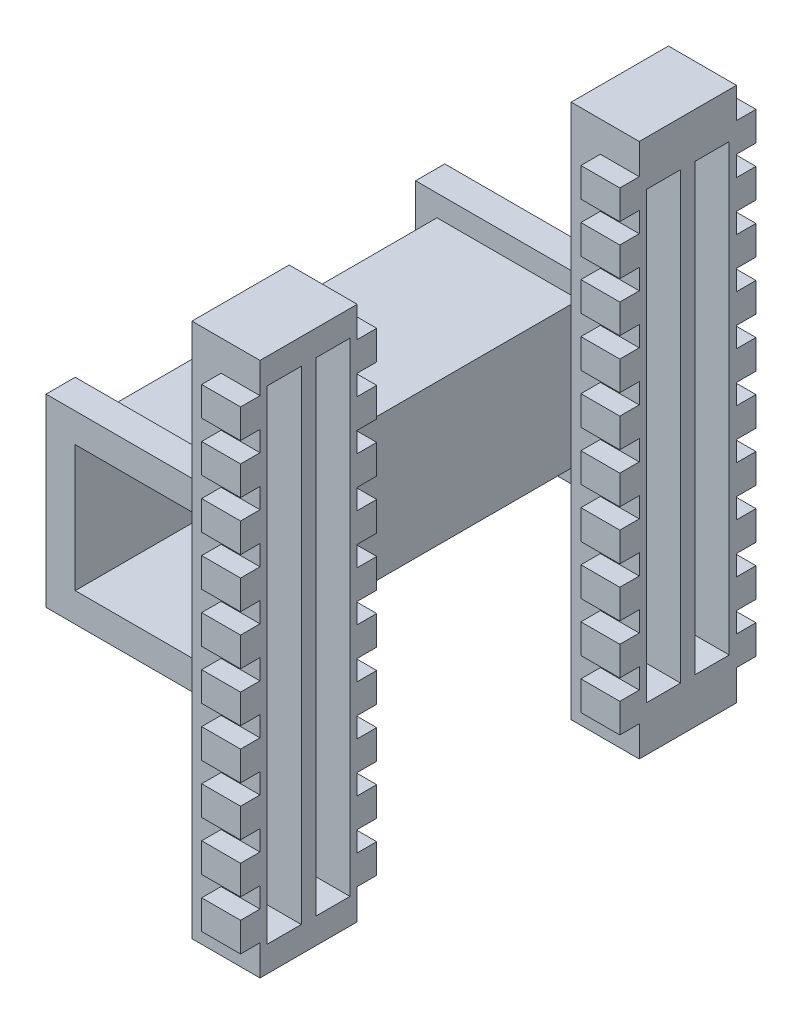
SolidWorks part; units mm, degrees
ref_plane "前视基准面" through (0, 0, 0) normal (0, 0, 1) x (1, 0, 0)
ref_plane "上视基准面" through (0, 0, 0) normal (0, 1, 0) x (1, 0, 0)
ref_plane "右视基准面" through (0, 0, 0) normal (1, 0, 0) x (0, 0, -1)
sketch "草图1" plane through (0, 0, 0) normal (0, 0, 1) x (1, 0, 0)
  line L0 (0.8, 0.8) -> (13.8, 0.8)
  line L5 (0, 0) -> (14.6, 0)
  line L6 (0, 0) -> (0, 14.6)
  line L7 (0, 14.6) -> (14.6, 14.6)
  line L9 (13.8, 0.8) -> (13.8, 13.8)
  line L10 (0.8, 13.8) -> (13.8, 13.8)
  line L11 (0.8, 0.8) -> (0.8, 13.8)
  line L13 (16.8, 14.6) -> (16.8, 0)
  line L15 (16.8, 7.3) -> (16.8, 34.8)
  line L16 (16.8, 7.3) -> (16.8, -20.2)
  line L17 (16.8, 34.8) -> (23.8, 34.8)
  line L18 (23.8, 34.8) -> (23.8, -20.2)
  line L19 (23.8, -20.2) -> (16.8, -20.2)
  line L23 (14.6, 14.6) -> (14.6, 0)
  line L24 (16.8, 0) -> (16.8, 14.6)
  line L28 (14.6, -2.2) -> (-2.2, -2.2)
  line L29 (-2.2, -2.2) -> (-2.2, 16.8)
  line L30 (-2.2, 16.8) -> (16.8, 16.8)
  line L31 (16.8, 16.8) -> (16.8, -2.2)
  line L32 (16.8, -2.2) -> (14.6, -2.2)
  line L34 (14.6, 0) -> (14.6, 14.6) construction
  point P14 (0, 0)
  dimension "D1" = 0.8
extrude "凸台-拉伸4" add sketch "草图1" along normal mid plane 41 contours L7 L23 L5 L6 | L10 L9 L0 L11
extrude "凸台-拉伸8" add sketch "草图1<12>" along normal mid plane 41 contours L32 L16 L13 L15 L30 L29 L28 L7 L23 L5 L6 region at (16.5313, 10.95, 0)
sketch "草图1<12>" plane through (0, 0, 0) normal (0, 0, 1) x (1, 0, 0) same geometry as "草图1"
extrude "切除-拉伸3" cut sketch "草图1<13>" against normal mid plane 35 contours L32 L28 L29 L30 L31 | L5 L23 L7 L6
sketch "草图1<13>" plane through (0, 0, 0) normal (0, 0, 1) x (1, 0, 0) same geometry as "草图1"
extrude "凸台-拉伸9" add sketch "草图1<14>" along normal mid plane 53 contours L19 L18 L17 L15 L13 L16 region at (20.3, 7.3, 0)
sketch "草图1<14>" plane through (0, 0, 0) normal (0, 0, 1) x (1, 0, 0) same geometry as "草图1"
extrude "切除-拉伸4" cut sketch "草图1<15>" against normal mid plane 25 contours L18 L19 L16 L15 L17
sketch "草图1<15>" plane through (0, 0, 0) normal (0, 0, 1) x (1, 0, 0) same geometry as "草图1"
sketch "草图6" plane through (0, 0, -26.5) normal (0, 0, -1) x (-1, 0, 0)
  line L3 (-23.8, 31.66) -> (-19.8, 31.66)
  line L5 (-23.8, 31.66) -> (-23.8, 28.66)
  line L7 (-23.8, 28.66) -> (-19.8, 28.66)
  line L8 (-23.8, -20.2) -> (-16.8, -20.2)
  line L9 (-19.8, 31.66) -> (-19.8, 28.66)
  line L10 (-16.8, -20.2) -> (-16.8, 34.8)
  line L11 (-23.8, 31.66) -> (-19.8, 28.66) construction
  line L12 (-16.8, 34.8) -> (-23.8, 34.8)
  line L13 (-23.8, 28.66) -> (-19.8, 31.66) construction
  line L14 (-23.8, 34.8) -> (-23.8, -20.2)
  line L15 (-23.8, 26.58) -> (-19.8, 26.58)
  line L16 (-23.8, -20.2) -> (-16.8, -20.2)
  line L17 (-23.8, 26.58) -> (-23.8, 23.58)
  line L18 (-16.8, -20.2) -> (-16.8, 34.8)
  line L19 (-23.8, 23.58) -> (-19.8, 23.58)
  line L20 (-16.8, 34.8) -> (-23.8, 34.8)
  line L21 (-19.8, 26.58) -> (-19.8, 23.58)
  line L22 (-23.8, 26.58) -> (-19.8, 23.58) construction
  line L23 (-23.8, 23.58) -> (-19.8, 26.58) construction
  line L24 (-23.8, 21.5) -> (-19.8, 21.5)
  line L25 (-23.8, 21.5) -> (-23.8, 18.5)
  line L26 (-23.8, 18.5) -> (-19.8, 18.5)
  line L27 (-19.8, 21.5) -> (-19.8, 18.5)
  line L28 (-23.8, 21.5) -> (-19.8, 18.5) construction
  line L29 (-23.8, 18.5) -> (-19.8, 21.5) construction
  line L30 (-23.8, 16.42) -> (-19.8, 16.42)
  line L31 (-23.8, 16.42) -> (-23.8, 13.42)
  line L32 (-23.8, 13.42) -> (-19.8, 13.42)
  line L33 (-19.8, 16.42) -> (-19.8, 13.42)
  line L34 (-23.8, 16.42) -> (-19.8, 13.42) construction
  line L35 (-23.8, 13.42) -> (-19.8, 16.42) construction
  line L36 (-23.8, 11.34) -> (-19.8, 11.34)
  line L37 (-23.8, 11.34) -> (-23.8, 8.34)
  line L38 (-23.8, 8.34) -> (-19.8, 8.34)
  line L39 (-19.8, 11.34) -> (-19.8, 8.34)
  line L40 (-23.8, 11.34) -> (-19.8, 8.34) construction
  line L41 (-23.8, 8.34) -> (-19.8, 11.34) construction
  line L42 (-23.8, 6.26) -> (-19.8, 6.26)
  line L43 (-23.8, 6.26) -> (-23.8, 3.26)
  line L44 (-23.8, 3.26) -> (-19.8, 3.26)
  line L45 (-19.8, 6.26) -> (-19.8, 3.26)
  line L46 (-23.8, 6.26) -> (-19.8, 3.26) construction
  line L47 (-23.8, 3.26) -> (-19.8, 6.26) construction
  line L48 (-23.8, 1.1866) -> (-19.8, 1.1866)
  line L49 (-23.8, 1.1866) -> (-23.8, -1.8266)
  line L50 (-23.8, -1.8266) -> (-19.8, -1.8266)
  line L51 (-19.8, 1.1866) -> (-19.8, -1.8266)
  line L52 (-23.8, 1.1866) -> (-19.8, -1.8266) construction
  line L53 (-23.8, -1.8266) -> (-19.8, 1.1866) construction
  line L54 (-23.8, -3.9) -> (-19.8, -3.9)
  line L55 (-23.8, -3.9) -> (-23.8, -6.9)
  line L56 (-23.8, -6.9) -> (-19.8, -6.9)
  line L57 (-19.8, -3.9) -> (-19.8, -6.9)
  line L58 (-23.8, -3.9) -> (-19.8, -6.9) construction
  line L59 (-23.8, -6.9) -> (-19.8, -3.9) construction
  line L60 (-23.8, -8.98) -> (-19.8, -8.98)
  line L61 (-23.8, -8.98) -> (-23.8, -11.98)
  line L62 (-23.8, -11.98) -> (-19.8, -11.98)
  line L63 (-19.8, -8.98) -> (-19.8, -11.98)
  line L64 (-23.8, -8.98) -> (-19.8, -11.98) construction
  line L65 (-23.8, -11.98) -> (-19.8, -8.98) construction
  line L66 (-23.8, -14.06) -> (-19.8, -14.06)
  line L67 (-23.8, -14.06) -> (-23.8, -17.06)
  line L68 (-23.8, -17.06) -> (-19.8, -17.06)
  line L69 (-19.8, -14.06) -> (-19.8, -17.06)
  line L70 (-23.8, -14.06) -> (-19.8, -17.06) construction
  line L71 (-23.8, -17.06) -> (-19.8, -14.06) construction
  line L72 (-23.8, 34.8) -> (-23.8, -20.2)
  point P0 (-21.8, 30.16)
  point P27 (-21.8, 25.08)
  point P32 (-21.8, 20)
  point P37 (-21.8, 14.92)
  point P42 (-21.8, 9.84)
  point P47 (-21.8, 4.76)
  point P52 (-21.8, -0.32)
  point P57 (-21.8, -5.4)
  point P62 (-21.8, -10.48)
  point P67 (-21.8, -15.56)
  line M14 (-23.8, -20.2) -> (-16.8, -20.2)
  line M15 (-16.8, -20.2) -> (-16.8, 34.8)
  line M16 (-16.8, 34.8) -> (-23.8, 34.8)
  line M17 (-23.8, 34.8) -> (-23.8, -20.2)
  dimension "D1" = 0
extrude "切除-拉伸5" cut sketch "草图6" against normal blind 2 contours L66 L69 L68 L3 L9 L7 L15 L21 L19 L24 L27 L26 L30 L33 L32 L36 L39 L38 L42 L45 L44 L48 L51 L50 L54 L57 L56 L60 L63 L62 M17 M14 M15 M16 region at (19.6203, 7.3015, -26.5)
sketch "草图7" plane through (0, 0, -12.5) normal (0, 0, 1) x (1, 0, 0)
  line L0 (19.8, -17.06) -> (19.8, -14.06) construction
  line L1 (19.8, -14.06) -> (23.8, -14.06) construction
  line L2 (23.8, -14.06) -> (23.8, -17.06) construction
  line L3 (23.8, -17.06) -> (19.8, -17.06) construction
  line L4 (23.8, 34.8) -> (16.8, 34.8)
  line L5 (16.8, 34.8) -> (16.8, -20.2)
  line L6 (16.8, -20.2) -> (23.8, -20.2)
  line L7 (23.8, -20.2) -> (23.8, 34.8)
  line L8 (23.8, 34.8) -> (16.8, 34.8)
  line L9 (16.8, 34.8) -> (16.8, -20.2)
  line L10 (16.8, -20.2) -> (23.8, -20.2)
  line L11 (23.8, -20.2) -> (23.8, 34.8)
  line L12 (23.8, -11.98) -> (19.8, -11.98) construction
  line L13 (19.8, -11.98) -> (19.8, -8.98) construction
  line L14 (19.8, -8.98) -> (23.8, -8.98) construction
  line L15 (23.8, -8.98) -> (23.8, -11.98) construction
  line L16 (23.8, -6.9) -> (19.8, -6.9) construction
  line L17 (19.8, -6.9) -> (19.8, -3.9) construction
  line L18 (19.8, -3.9) -> (23.8, -3.9) construction
  line L19 (23.8, -3.9) -> (23.8, -6.9) construction
  line L20 (23.8, -1.8266) -> (19.8, -1.8266) construction
  line L21 (19.8, -1.8266) -> (19.8, 1.1866) construction
  line L22 (19.8, 1.1866) -> (23.8, 1.1866) construction
  line L23 (23.8, 1.1866) -> (23.8, -1.8266) construction
  line L24 (23.8, 3.26) -> (19.8, 3.26) construction
  line L25 (19.8, 3.26) -> (19.8, 6.26) construction
  line L26 (19.8, 6.26) -> (23.8, 6.26) construction
  line L27 (23.8, 6.26) -> (23.8, 3.26) construction
  line L28 (23.8, 8.34) -> (19.8, 8.34) construction
  line L29 (19.8, 8.34) -> (19.8, 11.34) construction
  line L30 (19.8, 11.34) -> (23.8, 11.34) construction
  line L31 (23.8, 11.34) -> (23.8, 8.34) construction
  line L32 (23.8, 13.42) -> (19.8, 13.42) construction
  line L33 (19.8, 13.42) -> (19.8, 16.42) construction
  line L34 (19.8, 16.42) -> (23.8, 16.42) construction
  line L35 (23.8, 16.42) -> (23.8, 13.42) construction
  line L36 (23.8, 18.5) -> (19.8, 18.5) construction
  line L37 (19.8, 18.5) -> (19.8, 21.5) construction
  line L38 (19.8, 21.5) -> (23.8, 21.5) construction
  line L39 (23.8, 21.5) -> (23.8, 18.5) construction
  line L40 (23.8, 23.58) -> (19.8, 23.58) construction
  line L41 (19.8, 23.58) -> (19.8, 26.58) construction
  line L42 (19.8, 26.58) -> (23.8, 26.58) construction
  line L43 (23.8, 26.58) -> (23.8, 23.58) construction
  line L44 (23.8, 28.66) -> (19.8, 28.66) construction
  line L45 (19.8, 28.66) -> (19.8, 31.66) construction
  line L46 (19.8, 31.66) -> (23.8, 31.66) construction
  line L47 (23.8, 31.66) -> (23.8, 28.66) construction
  line L48 (19.8, -17.06) -> (19.8, -14.06)
  line L49 (19.8, -14.06) -> (23.8, -14.06)
  line L50 (23.8, -14.06) -> (23.8, -17.06)
  line L51 (23.8, -17.06) -> (19.8, -17.06)
  line L52 (23.8, -11.98) -> (19.8, -11.98)
  line L53 (19.8, -11.98) -> (19.8, -8.98)
  line L54 (19.8, -8.98) -> (23.8, -8.98)
  line L55 (23.8, -8.98) -> (23.8, -11.98)
  line L56 (23.8, -6.9) -> (19.8, -6.9)
  line L57 (19.8, -6.9) -> (19.8, -3.9)
  line L58 (19.8, -3.9) -> (23.8, -3.9)
  line L59 (23.8, -3.9) -> (23.8, -6.9)
  line L60 (23.8, -1.8266) -> (19.8, -1.8266)
  line L61 (19.8, -1.8266) -> (19.8, 1.1866)
  line L62 (19.8, 1.1866) -> (23.8, 1.1866)
  line L63 (23.8, 1.1866) -> (23.8, -1.8266)
  line L64 (23.8, 3.26) -> (19.8, 3.26)
  line L65 (19.8, 3.26) -> (19.8, 6.26)
  line L66 (19.8, 6.26) -> (23.8, 6.26)
  line L67 (23.8, 6.26) -> (23.8, 3.26)
  line L68 (23.8, 8.34) -> (19.8, 8.34)
  line L69 (19.8, 8.34) -> (19.8, 11.34)
  line L70 (19.8, 11.34) -> (23.8, 11.34)
  line L71 (23.8, 11.34) -> (23.8, 8.34)
  line L72 (23.8, 13.42) -> (19.8, 13.42)
  line L73 (19.8, 13.42) -> (19.8, 16.42)
  line L74 (19.8, 16.42) -> (23.8, 16.42)
  line L75 (23.8, 16.42) -> (23.8, 13.42)
  line L76 (23.8, 18.5) -> (19.8, 18.5)
  line L77 (19.8, 18.5) -> (19.8, 21.5)
  line L78 (19.8, 21.5) -> (23.8, 21.5)
  line L79 (23.8, 21.5) -> (23.8, 18.5)
  line L80 (23.8, 23.58) -> (19.8, 23.58)
  line L81 (19.8, 23.58) -> (19.8, 26.58)
  line L82 (19.8, 26.58) -> (23.8, 26.58)
  line L83 (23.8, 26.58) -> (23.8, 23.58)
  line L84 (23.8, 28.66) -> (19.8, 28.66)
  line L85 (19.8, 28.66) -> (19.8, 31.66)
  line L86 (19.8, 31.66) -> (23.8, 31.66)
  line L87 (23.8, 31.66) -> (23.8, 28.66)
  line M5 (23.8, 34.8) -> (16.8, 34.8)
  line M6 (16.8, 34.8) -> (16.8, -20.2)
  line M7 (16.8, -20.2) -> (23.8, -20.2)
  line M8 (23.8, -20.2) -> (23.8, 34.8)
  dimension "D1" = 0
extrude "切除-拉伸6" cut sketch "草图7" against normal blind 2 contours L85 L86 L11 L51 L48 L49 L52 L53 L54 L56 L57 L58 L60 L61 L62 L64 L65 L66 L68 L69 L70 L72 L73 L74 L76 L77 L78 L80 L81 L82 L84 M5 M6 M7 M8 region at (19.6203, 7.3015, -12.5)
sketch "草图8" plane through (0, 0, 12.5) normal (0, 0, -1) x (-1, 0, 0)
  line L0 (-23.8, 13.42) -> (-19.8, 13.42) construction
  line L1 (-19.8, 13.42) -> (-19.8, 16.42) construction
  line L2 (-19.8, 16.42) -> (-23.8, 16.42) construction
  line L3 (-23.8, 16.42) -> (-23.8, 13.42) construction
  line L4 (-16.8, 34.8) -> (-23.8, 34.8)
  line L5 (-23.8, 34.8) -> (-23.8, -20.2)
  line L6 (-23.8, -20.2) -> (-16.8, -20.2)
  line L7 (-16.8, -20.2) -> (-16.8, 34.8)
  line L8 (-16.8, 34.8) -> (-23.8, 34.8)
  line L9 (-23.8, 34.8) -> (-23.8, -20.2)
  line L10 (-23.8, -20.2) -> (-16.8, -20.2)
  line L11 (-16.8, -20.2) -> (-16.8, 34.8)
  line L12 (-23.8, 18.5) -> (-19.8, 18.5) construction
  line L13 (-19.8, 18.5) -> (-19.8, 21.5) construction
  line L14 (-19.8, 21.5) -> (-23.8, 21.5) construction
  line L15 (-23.8, 21.5) -> (-23.8, 18.5) construction
  line L16 (-23.8, 23.58) -> (-19.8, 23.58) construction
  line L17 (-19.8, 23.58) -> (-19.8, 26.58) construction
  line L18 (-19.8, 26.58) -> (-23.8, 26.58) construction
  line L19 (-23.8, 26.58) -> (-23.8, 23.58) construction
  line L20 (-23.8, 28.66) -> (-19.8, 28.66) construction
  line L21 (-19.8, 28.66) -> (-19.8, 31.66) construction
  line L22 (-19.8, 31.66) -> (-23.8, 31.66) construction
  line L23 (-23.8, 31.66) -> (-23.8, 28.66) construction
  line L24 (-23.8, 8.34) -> (-19.8, 8.34) construction
  line L25 (-19.8, 8.34) -> (-19.8, 11.34) construction
  line L26 (-19.8, 11.34) -> (-23.8, 11.34) construction
  line L27 (-23.8, 11.34) -> (-23.8, 8.34) construction
  line L28 (-23.8, 3.26) -> (-19.8, 3.26) construction
  line L29 (-19.8, 3.26) -> (-19.8, 6.26) construction
  line L30 (-19.8, 6.26) -> (-23.8, 6.26) construction
  line L31 (-23.8, 6.26) -> (-23.8, 3.26) construction
  line L32 (-23.8, -1.8266) -> (-19.8, -1.8266) construction
  line L33 (-19.8, -1.8266) -> (-19.8, 1.1866) construction
  line L34 (-19.8, 1.1866) -> (-23.8, 1.1866) construction
  line L35 (-23.8, 1.1866) -> (-23.8, -1.8266) construction
  line L36 (-23.8, -6.9) -> (-19.8, -6.9) construction
  line L37 (-19.8, -6.9) -> (-19.8, -3.9) construction
  line L38 (-19.8, -3.9) -> (-23.8, -3.9) construction
  line L39 (-23.8, -3.9) -> (-23.8, -6.9) construction
  line L40 (-23.8, -11.98) -> (-19.8, -11.98) construction
  line L41 (-19.8, -11.98) -> (-19.8, -8.98) construction
  line L42 (-19.8, -8.98) -> (-23.8, -8.98) construction
  line L43 (-23.8, -8.98) -> (-23.8, -11.98) construction
  line L44 (-19.8, -17.06) -> (-19.8, -14.06) construction
  line L45 (-19.8, -14.06) -> (-23.8, -14.06) construction
  line L46 (-23.8, -14.06) -> (-23.8, -17.06) construction
  line L47 (-23.8, -17.06) -> (-19.8, -17.06) construction
  line L48 (-23.8, 13.42) -> (-19.8, 13.42)
  line L49 (-19.8, 13.42) -> (-19.8, 16.42)
  line L50 (-19.8, 16.42) -> (-23.8, 16.42)
  line L51 (-23.8, 16.42) -> (-23.8, 13.42)
  line L52 (-23.8, 18.5) -> (-19.8, 18.5)
  line L53 (-19.8, 18.5) -> (-19.8, 21.5)
  line L54 (-19.8, 21.5) -> (-23.8, 21.5)
  line L55 (-23.8, 21.5) -> (-23.8, 18.5)
  line L56 (-23.8, 23.58) -> (-19.8, 23.58)
  line L57 (-19.8, 23.58) -> (-19.8, 26.58)
  line L58 (-19.8, 26.58) -> (-23.8, 26.58)
  line L59 (-23.8, 26.58) -> (-23.8, 23.58)
  line L60 (-23.8, 28.66) -> (-19.8, 28.66)
  line L61 (-19.8, 28.66) -> (-19.8, 31.66)
  line L62 (-19.8, 31.66) -> (-23.8, 31.66)
  line L63 (-23.8, 31.66) -> (-23.8, 28.66)
  line L64 (-23.8, 8.34) -> (-19.8, 8.34)
  line L65 (-19.8, 8.34) -> (-19.8, 11.34)
  line L66 (-19.8, 11.34) -> (-23.8, 11.34)
  line L67 (-23.8, 11.34) -> (-23.8, 8.34)
  line L68 (-23.8, 3.26) -> (-19.8, 3.26)
  line L69 (-19.8, 3.26) -> (-19.8, 6.26)
  line L70 (-19.8, 6.26) -> (-23.8, 6.26)
  line L71 (-23.8, 6.26) -> (-23.8, 3.26)
  line L72 (-23.8, -1.8266) -> (-19.8, -1.8266)
  line L73 (-19.8, -1.8266) -> (-19.8, 1.1866)
  line L74 (-19.8, 1.1866) -> (-23.8, 1.1866)
  line L75 (-23.8, 1.1866) -> (-23.8, -1.8266)
  line L76 (-23.8, -6.9) -> (-19.8, -6.9)
  line L77 (-19.8, -6.9) -> (-19.8, -3.9)
  line L78 (-19.8, -3.9) -> (-23.8, -3.9)
  line L79 (-23.8, -3.9) -> (-23.8, -6.9)
  line L80 (-23.8, -11.98) -> (-19.8, -11.98)
  line L81 (-19.8, -11.98) -> (-19.8, -8.98)
  line L82 (-19.8, -8.98) -> (-23.8, -8.98)
  line L83 (-23.8, -8.98) -> (-23.8, -11.98)
  line L84 (-19.8, -17.06) -> (-19.8, -14.06)
  line L85 (-19.8, -14.06) -> (-23.8, -14.06)
  line L86 (-23.8, -14.06) -> (-23.8, -17.06)
  line L87 (-23.8, -17.06) -> (-19.8, -17.06)
  line M5 (-16.8, 34.8) -> (-23.8, 34.8)
  line M6 (-23.8, 34.8) -> (-23.8, -20.2)
  line M7 (-23.8, -20.2) -> (-16.8, -20.2)
  line M8 (-16.8, -20.2) -> (-16.8, 34.8)
  dimension "D1" = 0
extrude "切除-拉伸7" cut sketch "草图8" against normal blind 2 contours L87 L62 L61 L60 L9 L58 L57 L56 L54 L53 L52 L50 L49 L48 L66 L65 L64 L70 L69 L68 L74 L73 L72 L78 L77 L76 L82 L81 L80 L85 L84 M6 M7 M8 M5 region at (19.6203, 7.3015, 12.5)
sketch "草图9" plane through (0, 0, 26.5) normal (0, 0, 1) x (1, 0, 0)
  line L0 (19.8, -17.06) -> (19.8, -14.06) construction
  line L1 (19.8, -14.06) -> (23.8, -14.06) construction
  line L2 (23.8, -14.06) -> (23.8, -17.06) construction
  line L3 (23.8, -17.06) -> (19.8, -17.06) construction
  line L4 (16.8, -20.2) -> (23.8, -20.2)
  line L5 (23.8, -20.2) -> (23.8, 34.8)
  line L6 (23.8, 34.8) -> (16.8, 34.8)
  line L7 (16.8, 34.8) -> (16.8, -20.2)
  line L8 (16.8, -20.2) -> (23.8, -20.2)
  line L9 (23.8, -20.2) -> (23.8, 34.8)
  line L10 (23.8, 34.8) -> (16.8, 34.8)
  line L11 (16.8, 34.8) -> (16.8, -20.2)
  line L12 (23.8, -11.98) -> (19.8, -11.98) construction
  line L13 (19.8, -11.98) -> (19.8, -8.98) construction
  line L14 (19.8, -8.98) -> (23.8, -8.98) construction
  line L15 (23.8, -8.98) -> (23.8, -11.98) construction
  line L16 (23.8, -6.9) -> (19.8, -6.9) construction
  line L17 (19.8, -6.9) -> (19.8, -3.9) construction
  line L18 (19.8, -3.9) -> (23.8, -3.9) construction
  line L19 (23.8, -3.9) -> (23.8, -6.9) construction
  line L20 (23.8, -1.8266) -> (19.8, -1.8266) construction
  line L21 (19.8, -1.8266) -> (19.8, 1.1866) construction
  line L22 (19.8, 1.1866) -> (23.8, 1.1866) construction
  line L23 (23.8, 1.1866) -> (23.8, -1.8266) construction
  line L24 (23.8, 3.26) -> (19.8, 3.26) construction
  line L25 (19.8, 3.26) -> (19.8, 6.26) construction
  line L26 (19.8, 6.26) -> (23.8, 6.26) construction
  line L27 (23.8, 6.26) -> (23.8, 3.26) construction
  line L28 (23.8, 8.34) -> (19.8, 8.34) construction
  line L29 (19.8, 8.34) -> (19.8, 11.34) construction
  line L30 (19.8, 11.34) -> (23.8, 11.34) construction
  line L31 (23.8, 11.34) -> (23.8, 8.34) construction
  line L32 (23.8, 13.42) -> (19.8, 13.42) construction
  line L33 (19.8, 13.42) -> (19.8, 16.42) construction
  line L34 (19.8, 16.42) -> (23.8, 16.42) construction
  line L35 (23.8, 16.42) -> (23.8, 13.42) construction
  line L36 (23.8, 18.5) -> (19.8, 18.5) construction
  line L37 (19.8, 18.5) -> (19.8, 21.5) construction
  line L38 (19.8, 21.5) -> (23.8, 21.5) construction
  line L39 (23.8, 21.5) -> (23.8, 18.5) construction
  line L40 (23.8, 23.58) -> (19.8, 23.58) construction
  line L41 (19.8, 23.58) -> (19.8, 26.58) construction
  line L42 (19.8, 26.58) -> (23.8, 26.58) construction
  line L43 (23.8, 26.58) -> (23.8, 23.58) construction
  line L44 (23.8, 28.66) -> (19.8, 28.66) construction
  line L45 (19.8, 28.66) -> (19.8, 31.66) construction
  line L46 (19.8, 31.66) -> (23.8, 31.66) construction
  line L47 (23.8, 31.66) -> (23.8, 28.66) construction
  line L48 (19.8, -17.06) -> (19.8, -14.06)
  line L49 (19.8, -14.06) -> (23.8, -14.06)
  line L50 (23.8, -14.06) -> (23.8, -17.06)
  line L51 (23.8, -17.06) -> (19.8, -17.06)
  line L52 (23.8, -11.98) -> (19.8, -11.98)
  line L53 (19.8, -11.98) -> (19.8, -8.98)
  line L54 (19.8, -8.98) -> (23.8, -8.98)
  line L55 (23.8, -8.98) -> (23.8, -11.98)
  line L56 (23.8, -6.9) -> (19.8, -6.9)
  line L57 (19.8, -6.9) -> (19.8, -3.9)
  line L58 (19.8, -3.9) -> (23.8, -3.9)
  line L59 (23.8, -3.9) -> (23.8, -6.9)
  line L60 (23.8, -1.8266) -> (19.8, -1.8266)
  line L61 (19.8, -1.8266) -> (19.8, 1.1866)
  line L62 (19.8, 1.1866) -> (23.8, 1.1866)
  line L63 (23.8, 1.1866) -> (23.8, -1.8266)
  line L64 (23.8, 3.26) -> (19.8, 3.26)
  line L65 (19.8, 3.26) -> (19.8, 6.26)
  line L66 (19.8, 6.26) -> (23.8, 6.26)
  line L67 (23.8, 6.26) -> (23.8, 3.26)
  line L68 (23.8, 8.34) -> (19.8, 8.34)
  line L69 (19.8, 8.34) -> (19.8, 11.34)
  line L70 (19.8, 11.34) -> (23.8, 11.34)
  line L71 (23.8, 11.34) -> (23.8, 8.34)
  line L72 (23.8, 13.42) -> (19.8, 13.42)
  line L73 (19.8, 13.42) -> (19.8, 16.42)
  line L74 (19.8, 16.42) -> (23.8, 16.42)
  line L75 (23.8, 16.42) -> (23.8, 13.42)
  line L76 (23.8, 18.5) -> (19.8, 18.5)
  line L77 (19.8, 18.5) -> (19.8, 21.5)
  line L78 (19.8, 21.5) -> (23.8, 21.5)
  line L79 (23.8, 21.5) -> (23.8, 18.5)
  line L80 (23.8, 23.58) -> (19.8, 23.58)
  line L81 (19.8, 23.58) -> (19.8, 26.58)
  line L82 (19.8, 26.58) -> (23.8, 26.58)
  line L83 (23.8, 26.58) -> (23.8, 23.58)
  line L84 (23.8, 28.66) -> (19.8, 28.66)
  line L85 (19.8, 28.66) -> (19.8, 31.66)
  line L86 (19.8, 31.66) -> (23.8, 31.66)
  line L87 (23.8, 31.66) -> (23.8, 28.66)
  line M5 (16.8, -20.2) -> (23.8, -20.2)
  line M6 (23.8, -20.2) -> (23.8, 34.8)
  line M7 (23.8, 34.8) -> (16.8, 34.8)
  line M8 (16.8, 34.8) -> (16.8, -20.2)
  dimension "D1" = 0
extrude "切除-拉伸8" cut sketch "草图9" against normal blind 2 contours L85 L86 L9 L51 L48 L49 L52 L53 L54 L56 L57 L58 L60 L61 L62 L64 L65 L66 L68 L69 L70 L72 L73 L74 L76 L77 L78 L80 L81 L82 L84 M7 M8 M5 M6 region at (19.6203, 7.3015, 26.5)
sketch "草图10" plane through (23.8, 0, 0) normal (1, 0, 0) x (0, 0, -1)
  line L0 (18.75, 32.16) -> (15.25, 32.16)
  line L3 (-19.5, 30.16) -> (-19.5, 32.16)
  line L4 (26.5, 30.16) -> (12.5, 30.16)
  line L5 (-20.2547, 32.16) -> (-23.7547, 32.16)
  line L6 (26.5, 31.66) -> (26.5, 28.66) construction
  line L7 (-18.75, 32.16) -> (-15.25, 32.16)
  line L8 (15.25, -17.56) -> (15.25, 32.16)
  line L11 (-19.5, -15.56) -> (-19.5, -17.56)
  line L12 (-18.75, -17.56) -> (-15.25, -17.56)
  line L13 (-20.2547, -17.56) -> (-23.7547, -17.56)
  line L14 (-23.7547, -17.56) -> (-23.7547, 32.16)
  line L15 (-20.2547, 32.16) -> (-20.2547, -17.56)
  line L16 (12.5, 31.66) -> (12.5, 28.66) construction
  line L17 (-15.25, -17.56) -> (-15.25, 32.16)
  line L18 (-18.75, 32.16) -> (-18.75, -17.56)
  line L20 (12.5, -15.56) -> (26.5, -15.56)
  line L21 (12.5, -14.06) -> (12.5, -17.06) construction
  line L22 (26.5, -14.06) -> (26.5, -17.06) construction
  line L25 (18.75, -17.56) -> (15.25, -17.56)
  line L26 (18.75, 32.16) -> (18.75, -17.56)
  line L27 (20.2547, 32.16) -> (23.7547, 32.16)
  line L28 (23.7547, -17.56) -> (23.7547, 32.16)
  line L29 (20.2547, -17.56) -> (23.7547, -17.56)
  line L30 (20.2547, 32.16) -> (20.2547, -17.56)
extrude "切除-拉伸9" cut sketch "草图10" against normal blind 4 contours L15 L5 L14 L13 | L7 L18 L12 L17 | L26 L4 L8 L20 | L4 L30 L20 L28 region at (23.8, 7.3, -17) region at (23.8, 7.3, -22.0047) region at (23.8, 7.3, 22.0047) region at (23.8, 7.3, 17)
